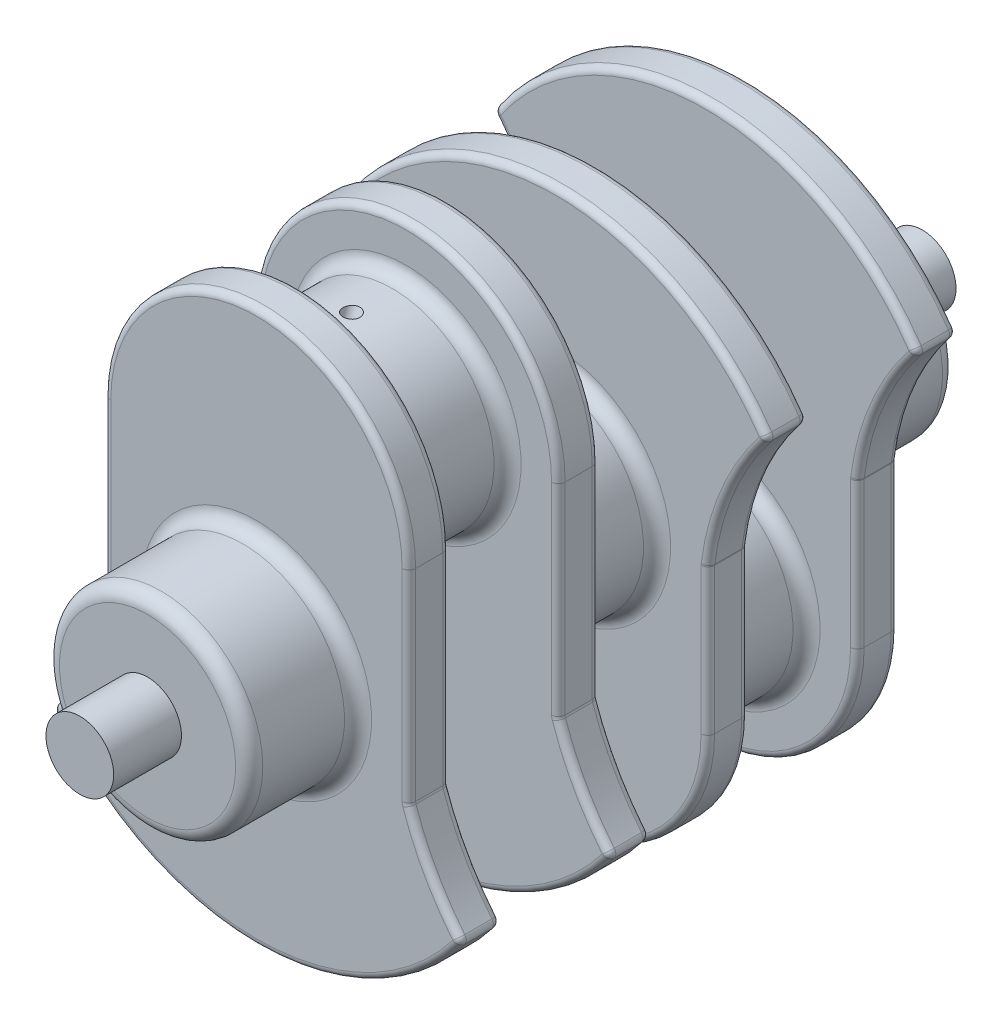
SolidWorks part; units mm, degrees
material "AISI 4340 Steel, normalized"
ref_plane "Front Plane" through (0, 0, 0) normal (0, 0, 1) x (1, 0, 0)
ref_plane "Top Plane" through (0, 0, 0) normal (0, 1, 0) x (1, 0, 0)
ref_plane "Right Plane" through (0, 0, 0) normal (1, 0, 0) x (0, 0, -1)
sketch "Sketch1" plane through (0, 0, 0) normal (0, 0, 1) x (1, 0, 0)
  circle A0 centre (0, 0) radius 30
  dimension "D1" = 30
extrude "Boss-Extrude1" add sketch "Sketch1" along normal blind 32.13
sketch "Sketch8" plane through (0, 0, 0) normal (0, 0, -1) x (-1, 0, 0)
  line L0 (-45, 43.2) -> (-45, -16.687)
  line L1 (45, 43.2) -> (45, -16.687)
  arc A0 (45, 43.2) -> (-45, 43.2) centre (0, 43.2) ccw
  arc A5 (-60.4975, -44.3289) -> (60.4975, -44.3289) centre (0, 0) ccw
  arc A6 (-45, -16.687) -> (-60.4975, -44.3289) centre (-125, 10) cw
  arc A7 (45, -16.687) -> (60.4975, -44.3289) centre (125, 10) ccw
  dimension "D1" = 45
  dimension "D2" = 75
  dimension "D3" = 43.2
  dimension "D5" = 10
  dimension "D6" = 125
extrude "Boss-Extrude5" add sketch "Sketch8" along normal blind 12
sketch "Sketch2" plane through (0, 0, 32.13) normal (0, 0, 1) x (1, 0, 0)
  circle A0 centre (0, 0) radius 10
  dimension "D1" = 10
extrude "Boss-Extrude2" add sketch "Sketch2" along normal blind 20
sketch "Sketch9" plane through (0, 0, -12) normal (0, 0, -1) x (-1, 0, 0)
  circle A0 centre (0, 43.2) radius 30
  dimension "D2" = 30
  dimension "D1" = 43.2
extrude "Boss-Extrude6" add sketch "Sketch9" along normal blind 32.13
ref_plane "Plane4" through (0, 0, -88.26) normal (0, 0, -1) x (-1, 0, 0)
sketch "Sketch10" plane through (0, 0, -44.13) normal (0, 0, -1) x (-1, 0, 0)
  line L0 (-45, -43.2) -> (-45, 0)
  line L1 (45, -43.2) -> (45, 0)
  arc A0 (-45, -43.2) -> (45, -43.2) centre (0, -43.2) ccw
  arc A1 (-45, 0) -> (-62.6932, 41.1651) centre (-125, -10) ccw
  arc A2 (45, 0) -> (62.6932, 41.1651) centre (125, -10) cw
  arc A3 (-62.6932, 41.1651) -> (62.6932, 41.1651) centre (0, 0) cw
  dimension "D1" = 45
  dimension "D5" = 10
  dimension "D3" = 75
  dimension "D2" = 43.2
  dimension "D4" = 125
extrude "Boss-Extrude7" add sketch "Sketch10" along normal blind 12 from surface starting at plane "Plane4"
ref_plane "Plane3" through (0, 0, -132.39) normal (0, 0, -1) x (-1, 0, 0)
sketch "Sketch12" plane through (0, 0, -132.39) normal (0, 0, -1) x (-1, 0, 0)
  line L2 (45, -43.2) -> (45, 0)
  line L3 (45, -43.2) -> (45, 0)
  line L4 (-45, 0) -> (-45, -43.2)
  line L5 (-45, 0) -> (-45, -43.2)
  arc A12 (-45, -43.2) -> (45, -43.2) centre (0, -43.2) ccw
  arc A13 (62.6932, 41.1651) -> (45, 0) centre (125, -10) ccw
  arc A14 (62.6932, 41.1651) -> (-62.6932, 41.1651) centre (0, 0) ccw
  arc A15 (-45, 0) -> (-62.6932, 41.1651) centre (-125, -10) ccw
  arc A16 (-45, -43.2) -> (45, -43.2) centre (0, -43.2) ccw
  arc A17 (62.6932, 41.1651) -> (45, 0) centre (125, -10) ccw
  arc A18 (62.6932, 41.1651) -> (-62.6932, 41.1651) centre (0, 0) ccw
  arc A19 (-45, 0) -> (-62.6932, 41.1651) centre (-125, -10) ccw
  dimension "D1" = 0
extrude "Boss-Extrude8" add sketch "Sketch12" along normal blind 12
sketch "Sketch14" plane through (0, 0, -100.26) normal (0, 0, -1) x (-1, 0, 0)
  circle A0 centre (0, -43.2) radius 30
  dimension "D2" = 30
  dimension "D1" = 43.2
extrude "Boss-Extrude9" add sketch "Sketch14" along normal up to next
sketch "Sketch15" plane through (0, 0, -144.39) normal (0, 0, -1) x (-1, 0, 0)
  circle A1 centre (0, 0) radius 30
  circle A2 centre (0, 0) radius 30
  dimension "D1" = 0
extrude "Boss-Extrude10" add sketch "Sketch15" along normal blind 32.13
sketch "Sketch16" plane through (0, 0, -176.52) normal (0, 0, -1) x (-1, 0, 0)
  circle A1 centre (0, 0) radius 10
  circle A2 centre (0, 0) radius 10
  dimension "D1" = 0
extrude "Boss-Extrude11" add sketch "Sketch16" along normal blind 20
sketch "Sketch18" plane through (0, 0, -44.13) normal (0, 0, -1) x (-1, 0, 0)
  line L2 (-45, 43.2) -> (-45, -16.687)
  line L3 (-45, 43.2) -> (-45, -16.687)
  line L4 (45, -16.687) -> (45, 43.2)
  line L5 (45, -16.687) -> (45, 43.2)
  arc A4 (45, 43.2) -> (-45, 43.2) centre (0, 43.2) ccw
  arc A5 (-60.4975, -44.3289) -> (-45, -16.687) centre (-125, 10) ccw
  arc A6 (-60.4975, -44.3289) -> (60.4975, -44.3289) centre (0, 0) ccw
  arc A7 (45, -16.687) -> (60.4975, -44.3289) centre (125, 10) ccw
  arc A8 (45, 43.2) -> (-45, 43.2) centre (0, 43.2) ccw
  arc A9 (-60.4975, -44.3289) -> (-45, -16.687) centre (-125, 10) ccw
  arc A10 (-60.4975, -44.3289) -> (60.4975, -44.3289) centre (0, 0) ccw
  arc A11 (45, -16.687) -> (60.4975, -44.3289) centre (125, 10) ccw
  dimension "D1" = 0
extrude "Boss-Extrude12" add sketch "Sketch18" along normal blind 12
sketch "Sketch19" plane through (0, 0, -56.13) normal (0, 0, -1) x (-1, 0, 0)
  circle A1 centre (0, 0) radius 30
  circle A2 centre (0, 0) radius 30
  dimension "D1" = 0
extrude "Boss-Extrude13" add sketch "Sketch19" along normal up to next
fillet "Fillet1" radius 2 32 edges at (0, -75, -44.13) (-51.4387, -31.2424, -44.13) (-45, 13.2565, -44.13) (45, 13.2565, -44.13) (51.4387, -31.2424, -44.13) (0, -75, -56.13) (-51.4387, -31.2424, -56.13) (-45, 13.2565, -56.13) (0, 88.2, -56.13) (45, 13.2565, -56.13) (51.4387, -31.2424, -56.13) (60.4975, -44.3289, -50.13) (45, -16.687, -50.13) (-45, -16.687, -50.13) (-60.4975, -44.3289, -50.13) (0, 88.2, -44.13) (45, 13.2565, 0) (51.4387, -31.2424, 0) (0, -75, 0) (-51.4387, -31.2424, 0) (-45, 13.2565, 0) (0, 88.2, -12) (45, 13.2565, -12) (51.4387, -31.2424, -12) (0, -75, -12) (-51.4387, -31.2424, -12) (-45, 13.2565, -12) (-45, -16.687, -6) (-60.4975, -44.3289, -6) (60.4975, -44.3289, -6) (45, -16.687, -6) (0, 88.2, 0)
fillet "Fillet2" radius 2 16 edges at (0, 75, -132.39) (50.9294, 21.8364, -132.39) (45, -21.6, -132.39) (0, -88.2, -132.39) (-45, -21.6, -132.39) (-50.9294, 21.8364, -132.39) (50.9294, 21.8364, -144.39) (45, -21.6, -144.39) (0, -88.2, -144.39) (-45, -21.6, -144.39) (-50.9294, 21.8364, -144.39) (-62.6932, 41.1651, -138.39) (-45, 0, -138.39) (45, 0, -138.39) (62.6932, 41.1651, -138.39) (0, 75, -144.39)
fillet "Fillet3" radius 2 16 edges at (45, -21.6, -88.26) (50.9294, 21.8364, -88.26) (0, 75, -88.26) (-50.9294, 21.8364, -88.26) (-45, -21.6, -88.26) (0, -88.2, -88.26) (45, -21.6, -100.26) (50.9294, 21.8364, -100.26) (-50.9294, 21.8364, -100.26) (-45, -21.6, -100.26) (0, -88.2, -100.26) (45, 0, -94.26) (62.6932, 41.1651, -94.26) (-62.6932, 41.1651, -94.26) (-45, 0, -94.26) (0, 75, -100.26)
fillet "Fillet5" radius 4 2 edges at (30, 0, 32.13) (30, 0, 0)
fillet "Fillet6" radius 4 2 edges at (-30, 0, -144.39) (-30, 0, -176.52)
ref_plane "Plane5" through (0, 31.75, 0) normal (0, 1, 0) x (1, 0, 0)
sketch "Sketch20" plane through (0, 0, 0) normal (1, 0, 0) x (0, 0, -1)
  line L1 (100.26, -73.2) -> (100.26, -13.2)
  line L2 (100.26, -73.2) -> (100.26, -13.2)
  dimension "D1" = 0
ref_plane "Plane6" through (0, -73.2, 0) normal (0, 1, 0) x (1, 0, 0)
sketch "Sketch21" plane through (0, 31.75, 0) normal (0, 1, 0) x (1, 0, 0)
  line L2 (-30, 172.52) -> (30, 172.52) construction
  line L3 (-30, 172.52) -> (-30, 148.39) construction
  line L4 (-30, 148.39) -> (30, 148.39) construction
  line L5 (30, 172.52) -> (30, 148.39) construction
  circle A0 centre (0, 160.455) radius 2.5
  point P10 (0, 172.52)
  point P11 (30, 160.455)
  dimension "D1" = 5
sketch "Sketch27" plane through (0, 0, 0) normal (0, 0, 1) x (1, 0, 0)
  line L0 (0, 73.2) -> (0, -30) construction
  circle A1 centre (0, 43.2) radius 30
  circle A2 centre (0, 43.2) radius 30 construction
  circle A3 centre (0, 0) radius 30
  circle A4 centre (0, 0) radius 30 construction
  dimension "D1" = 0
  dimension "D2" = 0
ref_plane "Plane8" through (0, 73.2, 0) normal (0, -1, 0) x (-1, 0, 0)
ref_plane "Plane9" through (0, -30, 0) normal (0, -1, 0) x (-1, 0, 0)
sketch "Sketch28" plane through (0, -30, 0) normal (0, -1, 0) x (-1, 0, 0)
  line L1 (-30, -4) -> (30, -4) construction
  line L2 (-30, -4) -> (-30, -28.13) construction
  line L3 (-30, -28.13) -> (30, -28.13) construction
  line L4 (30, -4) -> (30, -28.13) construction
  line L5 (-30, -4) -> (30, -28.13) construction
  line L6 (-30, -28.13) -> (30, -4) construction
  circle A0 centre (0, -16.065) radius 2.5
  point P4 (0, -16.065)
  dimension "D1" = 5
sketch "Sketch29" plane through (0, 73.2, 0) normal (0, -1, 0) x (-1, 0, 0)
  line L1 (30, 44.13) -> (-30, 44.13) construction
  line L2 (30, 44.13) -> (30, 12) construction
  line L3 (30, 12) -> (-30, 12) construction
  line L4 (-30, 44.13) -> (-30, 12) construction
  line L5 (30, 44.13) -> (-30, 12) construction
  line L6 (30, 12) -> (-30, 44.13) construction
  circle A0 centre (0, 28.065) radius 2.5
  point P4 (0, 28.065)
sketch "Sketch31" plane through (0, 0, 0) normal (1, 0, 0) x (0, 0, -1)
  line L0 (28.065, 73.2) -> (-16.065, -30) construction
ref_plane "Plane10" through (0, 73.2, -28.065) normal (0, -0.9195, 0.3932) x (-1, 0, 0)
ref_plane "Plane11" through (0, -30, 16.065) normal (0, -0.9195, 0.3932) x (-1, 0, 0)
combine bodies "Combine1" operation type add bodies to combine 119 109 117
fillet "Fillet7" radius 4 6 edges at (-30, 43.2, -44.13) (-30, 43.2, -12) (-30, 0, -56.13) (-30, 0, -88.26) (-30, -43.2, -132.39) (-30, -43.2, -100.26)
sketch "Sketch39" plane through (0, -73.2, 0) normal (0, 1, 0) x (1, 0, 0)
  line L1 (30, 128.39) -> (-30, 128.39) construction
  line L2 (30, 128.39) -> (30, 104.26) construction
  line L3 (30, 104.26) -> (-30, 104.26) construction
  line L4 (-30, 128.39) -> (-30, 104.26) construction
  line L5 (30, 128.39) -> (-30, 104.26) construction
  line L6 (30, 104.26) -> (-30, 128.39) construction
  point P4 (0, 116.325)
sketch "Sketch40" plane through (0, 0, 0) normal (1, 0, 0) x (0, 0, -1)
  line L0 (160.455, 31.75) -> (116.325, -73.2) construction
  line L1 (172.52, 31.75) -> (148.39, 31.75) construction
ref_plane "Plane12" through (0, 31.75, -160.455) normal (0, -0.9218, 0.3876) x (-1, 0, 0)
ref_plane "Plane13" through (0, -73.2, -116.325) normal (0, -0.9218, 0.3876) x (-1, 0, 0)
sketch "Sketch47" plane through (0, 73.2, -28.065) normal (0, -0.9195, 0.3932) x (-1, 0, 0)
  ellipse E0 centre (0, 0) end of major axis (2.5, 0) minor radius 2.2987 construction
  ellipse E1 centre (0, 0) end of major axis (2.5, 0) minor radius 2.2987
extrude "Cut-Extrude1" cut sketch "Sketch47" along normal through all
sketch "Sketch48" plane through (0, -30, 16.065) normal (0, -0.9195, 0.3932) x (-1, 0, 0)
  ellipse E0 centre (0, 0) end of major axis (2.5, 0) minor radius 2.2987 construction
  ellipse E1 centre (0, 0) end of major axis (2.5, 0) minor radius 2.2987
extrude "Cut-Extrude2" cut sketch "Sketch48" against normal through all
sketch "Sketch49" plane through (0, -73.2, -116.325) normal (0, -0.9218, 0.3876) x (-1, 0, 0)
  circle A0 centre (0, 0) radius 2.5
  dimension "D1" = 5
extrude "Cut-Extrude3" cut sketch "Sketch49" against normal through all
sketch "Sketch50" plane through (0, 31.75, -160.455) normal (0, -0.9218, 0.3876) x (-1, 0, 0)
  circle A0 centre (0, 0) radius 2.5 construction
  circle A1 centre (0, 0) radius 2.5
extrude "Cut-Extrude4" cut sketch "Sketch50" along normal through all
equation "\"CRR\"= 43.2mm'Crank Radius"
equation "\"D1@Sketch9\"=\"CRR\""
equation "\"D1@Sketch14\"=\"CRR\""
equation "\"JR\" = 30mm'Journal Radius"
equation "\"D1@Sketch1\"=\"JR\""
equation "\"D2@Sketch9\"=\"JR\""
equation "\"D2@Sketch14\"=\"JR\""
equation "\"LT\"= 12mm'Lobe Thickness"
equation "\"D1@Boss-Extrude5\"=\"LT\""
equation "\"D1@Boss-Extrude7\"=\"LT\""
equation "\"D1@Boss-Extrude8\"=\"LT\""
equation "\"D1@Boss-Extrude12\"=\"LT\""
equation "\"D3@Sketch8\"=\"CRR\""
equation "\"D2@Sketch10\"=\"CRR\""
equation "\"JL\"= 24.13 + 2 * ( \"JF\" )'Journal Length"
equation "\"D1@Boss-Extrude1\"=\"JL\""
equation "\"D1@Boss-Extrude6\"=\"JL\""
equation "\"D1@Boss-Extrude10\"=\"JL\""
equation "\"LHD\"= 5mm'Lubrication Hole Diameter"
equation "\"D1@Sketch29\"=\"LHD\""
equation "\"JF\"= 4mm'Internal Journal Fillets"
equation "\"D1@Fillet7\"=\"JF\""
equation "\"D1@Fillet6\"=\"JF\""
equation "\"LR\" = 45mm'Lobe radius"
equation "\"CWR\" = 75mm'Counterweight Radius"
equation "\"D1@Sketch8\"=\"LR\""
equation "\"D2@Sketch8\"=\"CWR\""
equation "\"D3@Sketch10\"=\"CWR\""
equation "\"D1@Sketch10\"=\"LR\""
